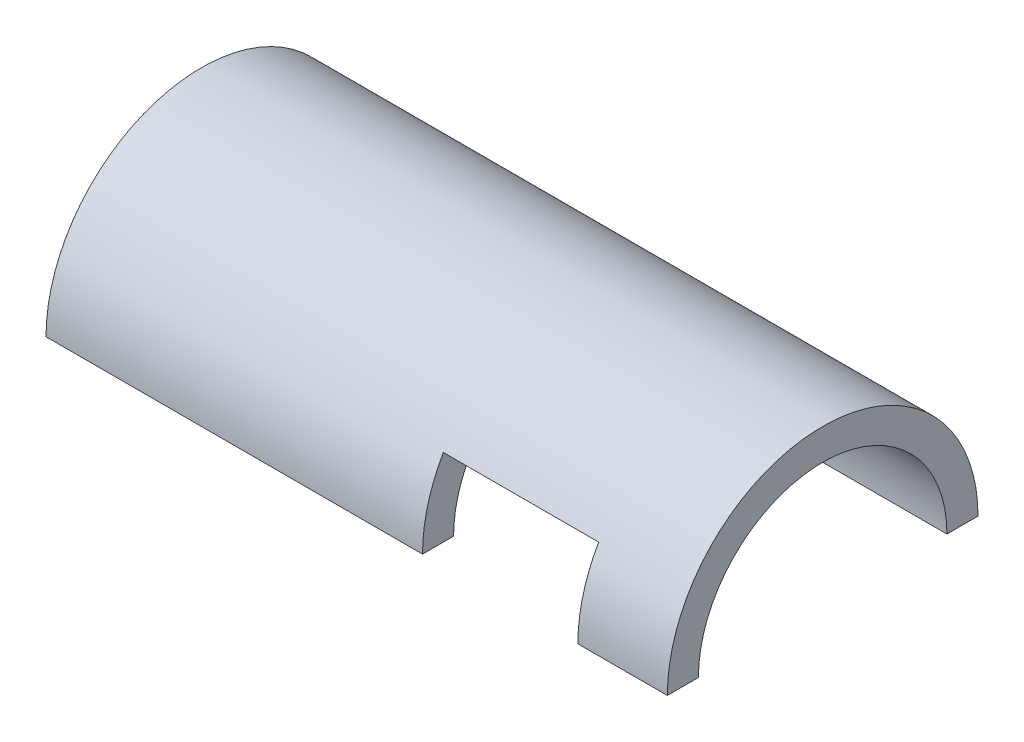
SolidWorks part; units mm, degrees
ref_plane "Front Plane" through (0, 0, 0) normal (0, 0, 1) x (1, 0, 0)
ref_plane "Top Plane" through (0, 0, 0) normal (0, 1, 0) x (1, 0, 0)
ref_plane "Right Plane" through (0, 0, 0) normal (1, 0, 0) x (0, 0, -1)
sketch "Sketch1" plane through (0, 0, 0) normal (1, 0, 0) x (0, 0, -1)
  line L0 (-31.75, 0) -> (-25.4, 0)
  line L1 (25.4, 0) -> (31.75, 0)
  arc A0 (-31.75, 0) -> (31.75, 0) centre (0, 0) cw
  arc A1 (-25.4, 0) -> (25.4, 0) centre (0, 0) cw
  dimension "D1" = 25.4
  dimension "D2" = 31.75
  dimension "D3" = 6.35
  dimension "D4" = 6.35
extrude "Boss-Extrude1" add sketch "Sketch1" against normal blind 127
sketch "Sketch2" plane through (0, 0, 0) normal (0, 0, 1) x (1, 0, 0)
  line L0 (-127, 0) -> (0, 0) construction
  line L1 (-50.038, 0) -> (-18.288, 0)
  line L2 (-50.038, 0) -> (-50.038, 15.875)
  line L3 (-50.038, 15.875) -> (-18.288, 15.875)
  line L4 (-18.288, 0) -> (-18.288, 15.875)
  line L5 (-127, 31.75) -> (-127, 0) construction
  dimension "D1" = 76.962
  dimension "D2" = 15.875
  dimension "D3" = 31.75
extrude "Cut-Extrude1" cut sketch "Sketch2" along normal blind 127
